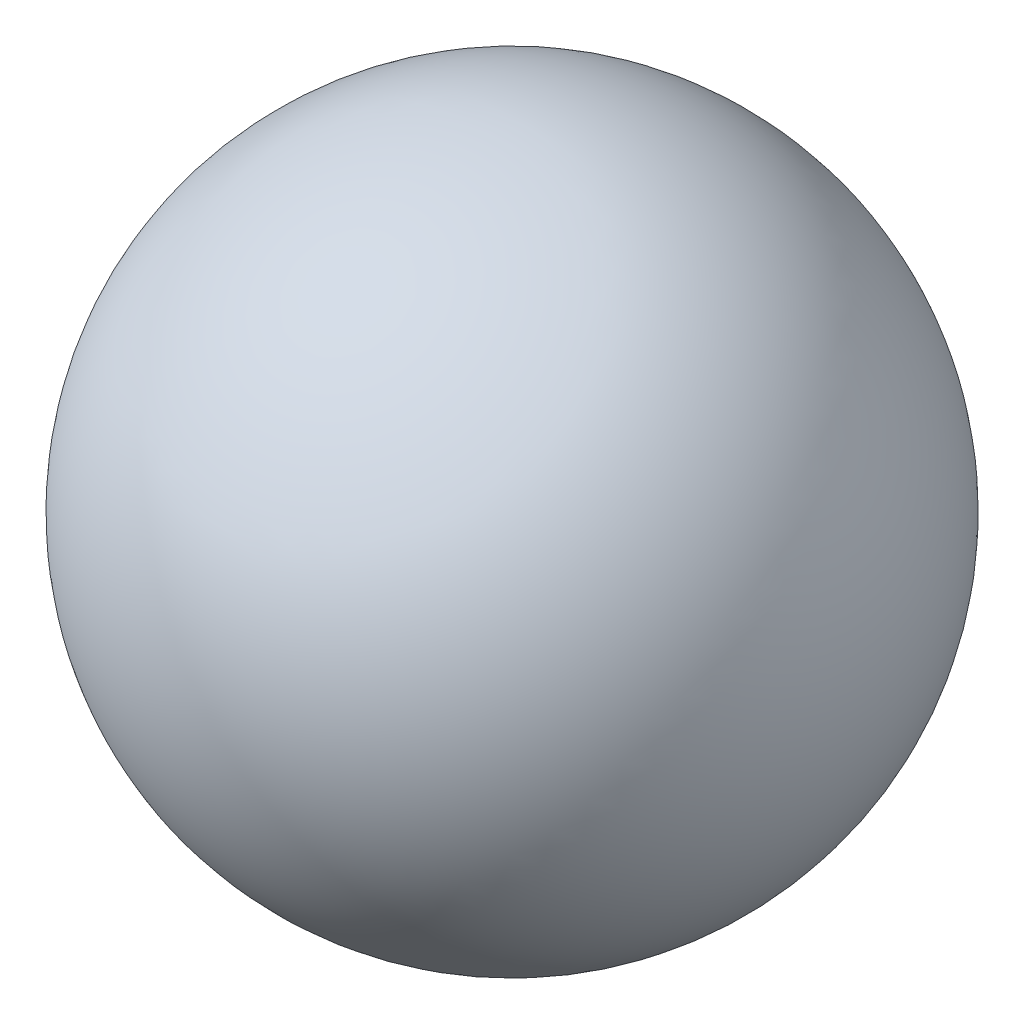
SolidWorks part; units mm, degrees
material "Chrome Stainless Steel"
ref_plane "Front Plane" through (0, 0, 0) normal (1, 0, 0) x (0, 1, 0)
ref_plane "Top Plane" through (0, 0, 0) normal (0, 0, 1) x (0, 1, 0)
ref_plane "Right Plane" through (0, 0, 0) normal (0, 1, 0) x (-1, 0, 0)
sketch "Sketch2" plane through (0, 0, 0) normal (1, 0, 0) x (0, 1, 0)
  line L0 (0, -9.525) -> (0, 9.525)
  arc A0 (0, 9.525) -> (0, -9.525) centre (0, 0) cw
  point P4 (0, 0)
  dimension "D1" = 19.05
revolve "Revolve1" add sketch "Sketch2" angle 360 about L0
equation "\"ball_diameter\"= 0.75in"
equation "\"D1@Sketch2\"=\"ball_diameter\""
